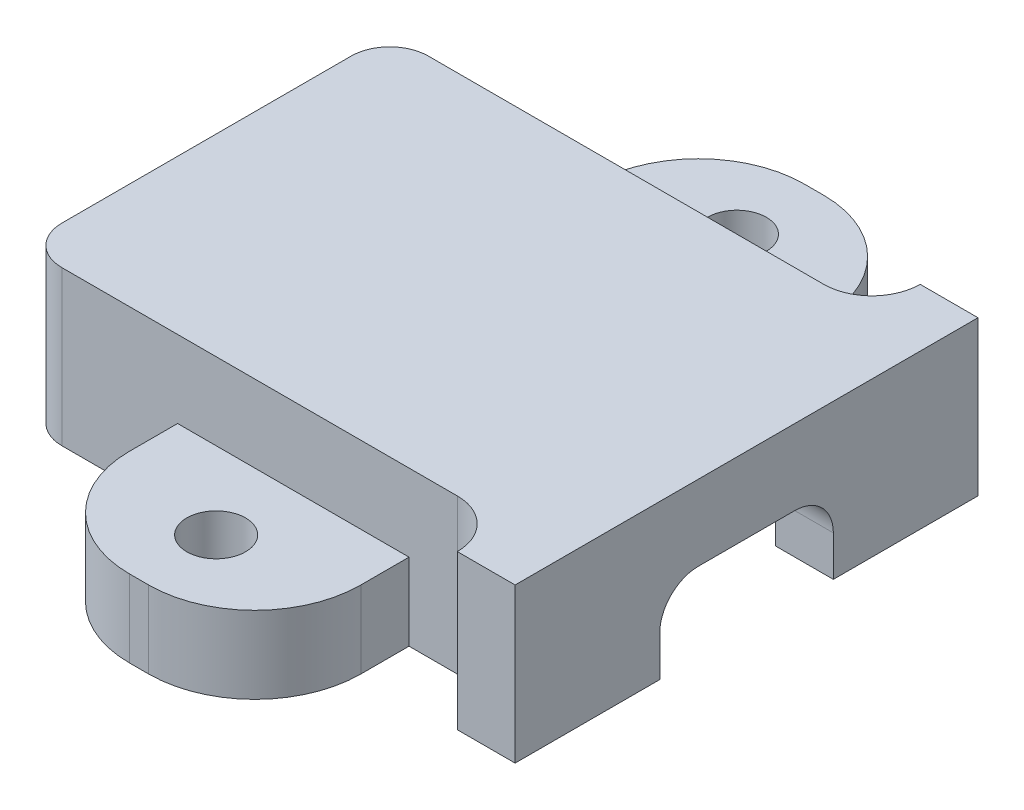
SolidWorks part; units mm, degrees
ref_plane "Front Plane" through (0, 0, 0) normal (0, 0, 1) x (1, 0, 0)
ref_plane "Top Plane" through (0, 0, 0) normal (0, 1, 0) x (1, 0, 0)
ref_plane "Right Plane" through (0, 0, 0) normal (1, 0, 0) x (0, 0, -1)
sketch "Sketch1" plane through (0, 0, 0) normal (0, 1, 0) x (1, 0, 0)
  line L0 (-1, -3) -> (23, -3)
  line L1 (0, 0) -> (22, 0)
  line L2 (0, 0) -> (0, 13)
  line L3 (0, 13) -> (22, 13)
  line L4 (22, 0) -> (22, 13)
  line L5 (25, -1) -> (25, 14)
  line L6 (-1, 16) -> (23, 16)
  line L7 (-3, -1) -> (-3, 14)
  line L8 (-3, -3) -> (25, -3) construction
  line L9 (25, -3) -> (25, 16) construction
  line L10 (-3, 16) -> (25, 16) construction
  line L11 (-3, -3) -> (-3, 16) construction
  line L12 (25, 14) -> (25, 16)
  line L13 (25, 16) -> (23, 16)
  line L14 (25, -1) -> (25, -3)
  line L15 (25, -3) -> (23, -3)
  arc A2 (-1, 16) -> (-3, 14) centre (-1, 14) ccw
  arc A3 (-1, -3) -> (-3, -1) centre (-1, -1) cw
  dimension "D1" = 22
  dimension "D2" = 13
  dimension "D3" = 3
extrude "Boss-Extrude1" add sketch "Sketch1" along normal blind 6
sketch "Sketch2" plane through (0, 6, 0) normal (0, 1, 0) x (1, 0, 0)
  line L0 (25, 14) -> (25, -1)
  line L1 (23, -3) -> (-1, -3)
  line L2 (-3, -1) -> (-3, 14)
  line L3 (-1, 16) -> (23, 16)
  line L4 (25, 16) -> (-1, 16) construction
  line L5 (23, 16) -> (25, 16)
  line L6 (25, -3) -> (25, 16) construction
  line L7 (25, 16) -> (25, 14)
  line L8 (25, -1) -> (25, -3)
  line L9 (-1, -3) -> (25, -3) construction
  line L10 (25, -3) -> (23, -3)
  arc A1 (-1, -3) -> (-3, -1) centre (-1, -1) cw
  arc A2 (-3, 14) -> (-1, 16) centre (-1, 14) cw
extrude "Boss-Extrude2" add sketch "Sketch2" along normal blind 2
sketch "Sketch3" plane through (0, 0, 0) normal (0, -1, 0) x (1, 0, 0)
  line L0 (-1, 3) -> (25, 3) construction
  line L1 (5, 3) -> (17, 3)
  line L2 (5, 3) -> (5, 5.5)
  line L3 (10.5, 11) -> (11.5, 11)
  line L4 (17, 3) -> (17, 5.5)
  line L5 (25, -16) -> (-1, -16) construction
  line L6 (17, -16) -> (5, -16)
  line L7 (17, -16) -> (17, -18.5)
  line L8 (11.5, -24) -> (10.5, -24)
  line L9 (5, -16) -> (5, -18.5)
  line L10 (25, 3) -> (25, -16) construction
  line L11 (-3, -14) -> (-3, 1) construction
  arc A0 (17, -18.5) -> (11.5, -24) centre (11.5, -18.5) cw
  arc A1 (10.5, -24) -> (5, -18.5) centre (10.5, -18.5) cw
  arc A2 (5, 5.5) -> (10.5, 11) centre (10.5, 5.5) cw
  arc A3 (11.5, 11) -> (17, 5.5) centre (11.5, 5.5) cw
  point P16 (17, -17.25)
  point P19 (17, -24)
  point P26 (17, 11)
  dimension "D7" = 5.5
  dimension "D1" = 8
  dimension "D2" = 8
  dimension "D3" = 8
  dimension "D4" = 8
  dimension "D5" = 8
  dimension "D6" = 8
extrude "Boss-Extrude3" add sketch "Sketch3" against normal up to surface (8 mm away) up to face at (6.8619, 8, -6.5)
sketch "Sketch4" plane through (0, 0, 0) normal (0, -1, 0) x (-1, 0, 0)
  line L0 (-17, 18.5) -> (-17, 16) construction
  line L2 (-10.5, 24) -> (-11.5, 24) construction
  line L3 (-11.5, -11) -> (-10.5, -11) construction
  line L4 (-5, -5.5) -> (-5, -3) construction
  circle A0 centre (-11, 20) radius 1.525
  circle A1 centre (-11, -7) radius 1.524
  point P9 (-11, 24)
  dimension "D1" = 3.048
  dimension "D2" = 3.05
  dimension "D3" = 6
  dimension "D4" = 4
  dimension "D5" = 4
  dimension "D6" = 6
extrude "Cut-Extrude1" cut sketch "Sketch4" against normal through all
sketch "Sketch5" plane through (25, 0, 0) normal (1, 0, 0) x (0, 0, -1)
  line L0 (-3, 0) -> (16, 0) construction
  line L1 (11, 0) -> (2, 0)
  line L2 (11, 0) -> (11, 4.0887)
  line L3 (11, 4.0887) -> (2, 4.0887)
  line L4 (2, 0) -> (2, 4.0887)
  line L5 (16, 8) -> (16, 0) construction
  line L6 (-3, 8) -> (-3, 0) construction
  dimension "D1" = 5
  dimension "D2" = 5
extrude "Cut-Extrude2" cut sketch "Sketch5" against normal through all
fillet "Fillet1" radius 2 4 edges at (-1.5, 4.0887, -2) (-1.5, 4.0887, -11) (23.5, 4.0887, -11) (23.5, 4.0887, -2)
sketch "Sketch6" plane through (0, 8, 0) normal (0, 1, 0) x (1, 0, 0)
  line L0 (-1, -3) -> (5, -3) construction
  line L1 (17, 16) -> (5, 16)
  line L2 (17, 16) -> (17, 29.009)
  line L3 (17, 29.009) -> (5, 29.009)
  line L4 (5, 16) -> (5, 29.009)
  line L5 (19.0682, -16.009) -> (3.2299, -16.009)
  line L6 (19.0682, -16.009) -> (19.0682, -3)
  line L7 (19.0682, -3) -> (3.2299, -3)
  line L8 (3.2299, -16.009) -> (3.2299, -3)
extrude "Cut-Extrude3" cut sketch "Sketch6" against normal blind 4
sketch "Sketch7" plane through (25, 0, 0) normal (1, 0, 0) x (0, 0, -1)
  line L0 (18.5, 4) -> (18.5, 0) construction
  line L1 (16, 8) -> (18.5, 8)
  line L2 (16, 8) -> (16, 0)
  line L3 (16, 0) -> (18.5, 0)
  line L4 (18.5, 8) -> (18.5, 0)
  line L5 (-3, 8) -> (-5.5, 8)
  line L6 (-3, 8) -> (-3, 0)
  line L7 (-3, 0) -> (-5.5, 0)
  line L8 (-5.5, 8) -> (-5.5, 0)
  line L9 (18.5, 0) -> (16, 0) construction
  line L10 (-5.5, 4) -> (-5.5, 0) construction
  line L11 (-3, 0) -> (-5.5, 0) construction
extrude "Boss-Extrude5" add sketch "Sketch7" against normal blind 3
fillet "Fillet3" radius 2.5 1 edges at (22, 4, -16)
fillet "Fillet4" radius 2.5 1 edges at (22, 4, 3)
